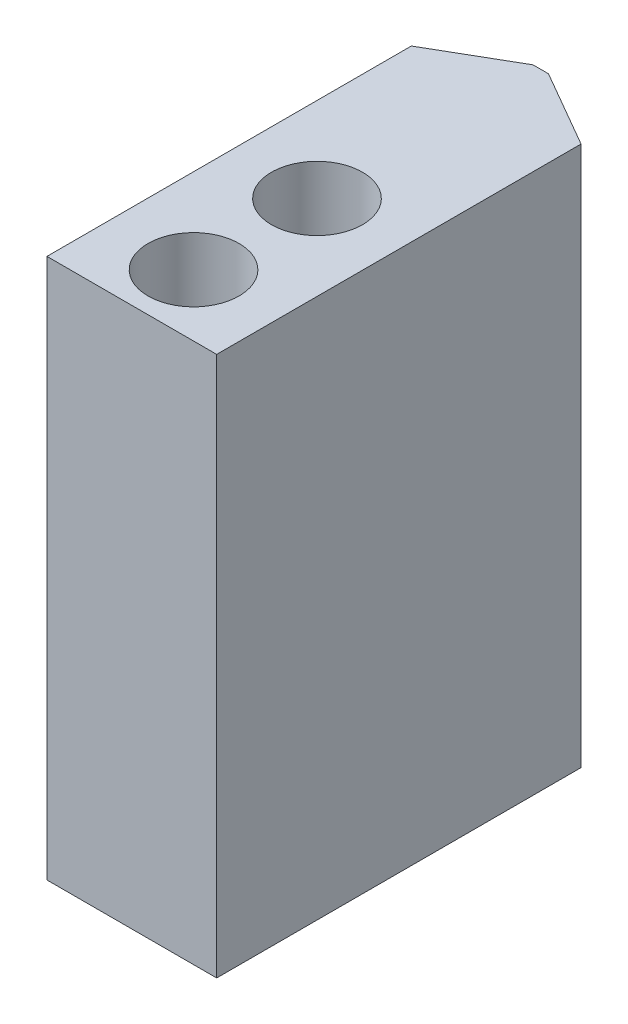
SolidWorks part; units mm, degrees
ref_plane "Front Plane" through (0, 0, 0) normal (0, 0, 1) x (1, 0, 0)
ref_plane "Top Plane" through (0, 0, 0) normal (0, 1, 0) x (1, 0, 0)
ref_plane "Right Plane" through (0, 0, 0) normal (1, 0, 0) x (0, 0, -1)
sketch "Sketch1" plane through (0, 0, 0) normal (0, 1, 0) x (1, 0, 0)
  line L0 (-5.5, -26.5) -> (5.5, -26.5)
  line L1 (5.5, -26.5) -> (5.5, -2.8868)
  line L2 (5.5, -2.8868) -> (0.5, 0)
  line L3 (0.5, 0) -> (-0.5, 0)
  line L4 (-0.5, 0) -> (-5.5, -2.8868)
  line L5 (-5.5, -2.8868) -> (-5.5, -26.5)
extrude "Boss-Extrude1" add sketch "Sketch1" along normal blind 35
sketch "Sketch2" plane through (0, 0, 0) normal (1, 0, 0) x (0, 0, -1)
  line L0 (-14.5, 35) -> (-11.55, 35)
  line L1 (-11.55, 35) -> (-11.55, 6)
  line L2 (-11.55, 6) -> (-12.9, 6)
  line L3 (-12.9, 6) -> (-12.9, 1.3)
  line L4 (-12.9, 1.3) -> (-12, 1.3)
  line L5 (-12, 1.3) -> (-12, 0)
  line L6 (-12, 0) -> (-14.5, 0)
  line L7 (-14.5, 0) -> (-14.5, 35)
  line L8 (-14.5, 0) -> (-14.5, 35) construction
revolve "Cut-Revolve1" cut sketch "Sketch2" angle 360 about L8 reverse direction yes
sketch "Sketch3" plane through (0, 0, 0) normal (1, 0, 0) x (0, 0, -1)
  line L0 (-22.5, 35) -> (-19.55, 35)
  line L1 (-19.55, 35) -> (-19.55, 6)
  line L2 (-19.55, 6) -> (-20.9, 6)
  line L3 (-20.9, 6) -> (-20.9, 1.3)
  line L4 (-20.9, 1.3) -> (-20, 1.3)
  line L5 (-20, 1.3) -> (-20, 0)
  line L6 (-20, 0) -> (-22.5, 0)
  line L7 (-22.5, 0) -> (-22.5, 35)
  line L8 (-22.5, 0) -> (-22.5, 35) construction
revolve "Cut-Revolve2" cut sketch "Sketch3" angle 360 about L8 reverse direction yes
ref_plane "Plane1" through (0, 6, 0) normal (0, 1, 0) x (1, 0, 0)
ref_plane "2DUMMY XY" through (0, 0, 0) normal (0, 1, 0) x (1, 0, 0)
ref_plane "2DUMMY XZ" through (0, 0, 22.5) normal (0, 0, 1) x (1, 0, 0)
ref_plane "2DUMMY YZ" through (0, 0, 0) normal (1, 0, 0) x (0, 0, -1)
ref_axis "2DUMMY X" through (-80.9, 0, 22.5) along (1, 0, 0)
ref_axis "2DUMMY Y" through (0, 0, 50) along (0, 0, -1)
ref_axis "2DUMMY Z" through (0, 50, 22.5) along (0, -1, 0)
sketch3d "2DUMMY"
  point P0 (0, 0, 22.5)
ref_plane "SCH 1 XY" through (0, 6, 0) normal (0, 1, 0) x (1, 0, 0)
ref_plane "SCH 1 XZ" through (0, 0, 14.5) normal (0, 0, 1) x (1, 0, 0)
ref_plane "SCH 1 YZ" through (0, 0, 0) normal (1, 0, 0) x (0, 0, -1)
ref_axis "SCH 1 X" through (-80.9, 6, 14.5) along (1, 0, 0)
ref_axis "SCH 1 Y" through (0, 6, 50) along (0, 0, -1)
ref_axis "SCH 1 Z" through (0, 50, 14.5) along (0, -1, 0)
sketch3d "SCH 1"
  point P0 (0, 6, 14.5)
ref_plane "SCH 2 XY" through (0, 6, 0) normal (0, 1, 0) x (1, 0, 0)
ref_plane "SCH 2 XZ" through (0, 0, 22.5) normal (0, 0, 1) x (1, 0, 0)
ref_plane "SCH 2 YZ" through (0, 0, 0) normal (1, 0, 0) x (0, 0, -1)
ref_axis "SCH 2 X" through (-80.9, 6, 22.5) along (1, 0, 0)
ref_axis "SCH 2 Y" through (0, 6, 50) along (0, 0, -1)
ref_axis "SCH 2 Z" through (0, 50, 22.5) along (0, -1, 0)
sketch3d "SCH 2"
  point P0 (0, 6, 22.5)
other "Freeze***"
